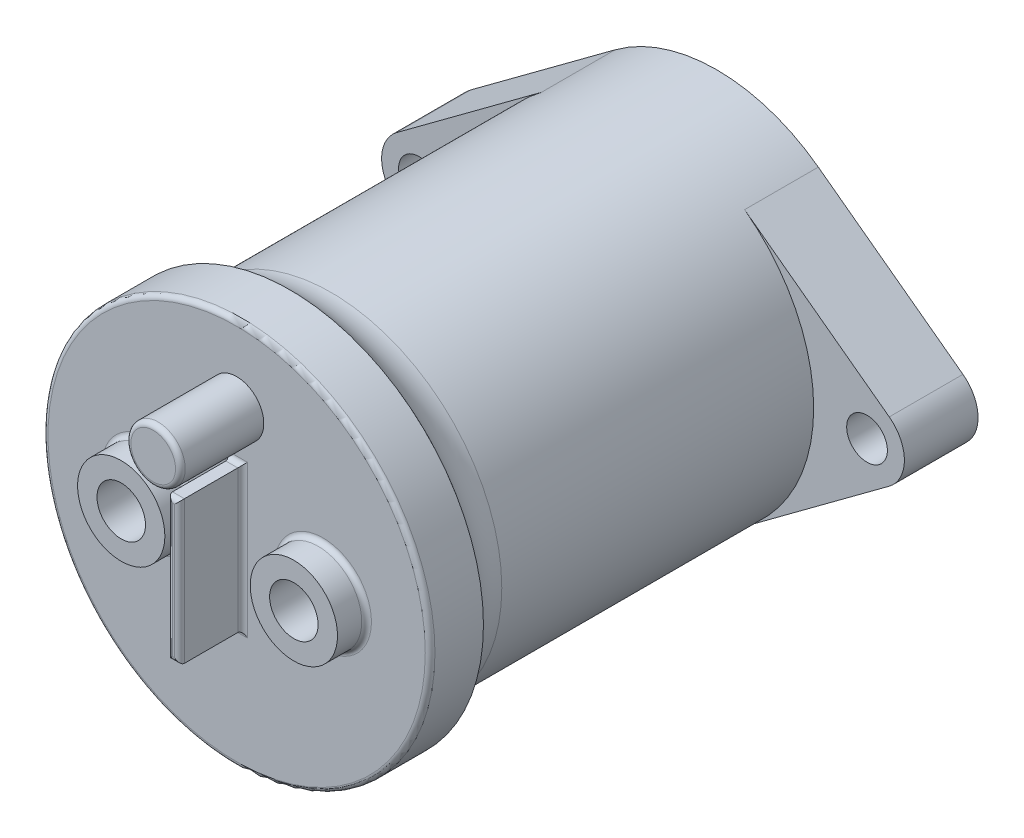
SolidWorks part; units mm, degrees
material "Custom Plastic"
ref_plane "X-Y Datum" through (0, 0, 0) normal (0, 0, 1) x (1, 0, 0)
ref_plane "X-Z Datum" through (0, 0, 0) normal (0, 1, 0) x (1, 0, 0)
ref_plane "Y-Z Datum" through (0, 0, 0) normal (1, 0, 0) x (0, 0, -1)
sketch "Sketch2" plane through (0, 0, 0) normal (0, 0, 1) x (1, 0, 0)
  circle A0 centre (0, 0) radius 17.6
  dimension "D1" = 35.2
extrude "Boss-Extrude1" add sketch "Sketch2" along normal blind 52.5
sketch "Sketch3" plane through (0, 0, 0) normal (0, 0, 1) x (1, 0, 0)
  line L0 (-23.1, 0) -> (23.1, 0) construction
  line L1 (-26.95, 0) -> (26.95, 0) construction
  line L2 (-25.3917, 3.0937) -> (-10.4762, 14.1425)
  line L3 (-25.3917, -3.0937) -> (-10.4762, -14.1425)
  line L4 (0, 28.5555) -> (0, -28.5555) construction
  line L5 (25.3917, -3.0937) -> (10.4762, -14.1425)
  line L6 (25.3917, 3.0937) -> (10.4762, 14.1425)
  circle A0 centre (23.1, 0) radius 2.1
  circle A1 centre (-23.1, 0) radius 2.1
  circle A2 centre (23.1, 0) radius 3.85
  circle A3 centre (-23.1, 0) radius 3.85
  circle A6 centre (0, 0) radius 17.6 construction
  circle A8 centre (0, 0) radius 17.6
  circle A9 centre (0, 0) radius 17.6
  point P4 (0, 0)
  point P10 (0, 0)
  point P23 (0, 0)
  dimension "D2" = 4.2
  dimension "D1" = 46.2
  dimension "D3" = 53.9
  dimension "D4" = 0
extrude "Boss-Extrude2" add sketch "Sketch3" along normal blind 7.6 contours A9 A2 L6 | A9 L5 A2 | A9 A2 A0 | A9 A3 A1 | A9 A3 L3 | A9 L2 A3 region at (-18.5342, 0, 0) region at (-21.417, 3.3412, 0) region at (18.5342, 0, 0) region at (26.4412, 1.683, 0)
sketch "Sketch4" plane through (0, 0, 52.5) normal (0, 0, 1) x (1, 0, 0)
  line L0 (-8.9, 0) -> (8.9, 0) construction
  line L1 (-0.615, 7.35) -> (0.615, 7.35)
  line L2 (-0.615, 7.35) -> (-0.615, -7.35)
  line L3 (-0.615, -7.35) -> (0.615, -7.35)
  line L4 (0.615, 7.35) -> (0.615, -7.35)
  line L5 (-0.615, 7.35) -> (0.615, -7.35) construction
  line L6 (-0.615, -7.35) -> (0.615, 7.35) construction
  circle A0 centre (-8.9, 0) radius 2.5
  circle A1 centre (8.9, 0) radius 2.5
  circle A2 centre (-8.9, 0) radius 4.5
  circle A3 centre (8.9, 0) radius 4.5
  point P0 (0, 0)
  point P11 (0, 0)
  dimension "D4" = 5
  dimension "D5" = 9
  dimension "D1" = 1.23
  dimension "D2" = 14.7
  dimension "D3" = 17.8
extrude "Boss-Extrude3" add sketch "Sketch4" along normal blind 3.5 contours L2 L1 L4 L3
sketch "Sketch5" plane through (0, 0, 52.5) normal (0, 0, 1) x (1, 0, 0)
  line L4 (0.615, 7.35) -> (-0.615, 7.35)
  line L5 (0.615, -7.35) -> (0.615, 7.35)
  line L6 (-0.615, -7.35) -> (0.615, -7.35)
  line L7 (-0.615, 7.35) -> (-0.615, -7.35)
  line L8 (0.615, 7.35) -> (-0.615, 7.35)
  line L9 (0.615, -7.35) -> (0.615, 7.35)
  line L10 (-0.615, -7.35) -> (0.615, -7.35)
  line L11 (-0.615, 7.35) -> (-0.615, -7.35)
  circle A1 centre (8.9, 0) radius 4.5
  circle A2 centre (8.9, 0) radius 4.5
  circle A3 centre (-8.9, 0) radius 4.5
  circle A4 centre (-8.9, 0) radius 4.5
  circle A5 centre (8.9, 0) radius 2.5
  circle A6 centre (8.9, 0) radius 2.5
  circle A7 centre (-8.9, 0) radius 2.5
  circle A8 centre (-8.9, 0) radius 2.5
  circle M22 centre (0, 0) radius 17.6
  line M23 (0.615, 7.35) -> (0.615, -7.35)
  line M24 (0.615, -7.35) -> (-0.615, -7.35)
  line M25 (-0.615, -7.35) -> (-0.615, 7.35)
  line M26 (-0.615, 7.35) -> (0.615, 7.35)
  dimension "D1" = 0
  dimension "D2" = 0
  dimension "D3" = 0
  dimension "D4" = 0
  dimension "D5" = 0
extrude "Cut-Extrude1" cut sketch "Sketch5" against normal blind 3 contours A4 A2 M22 M26 M23 M24 M25 | A8 | A6 region at (8.9, 0, 52.5) region at (-8.9, 0, 52.5) region at (-17.1022, 0, 52.5)
sketch "Sketch7" plane through (0, 0, 49.5) normal (0, 0, 1) x (1, 0, 0)
  circle A0 centre (0, 0) radius 19.95
  dimension "D1" = 39.9
extrude "Boss-Extrude5" add sketch "Sketch7" against normal blind 5.5
fillet "Fillet3" radius 5 1 edges at (17.6, 0, 44)
fillet "Fillet4" radius 0.5 11 edges at (-0.615, 0, 56) (0, 7.35, 56) (0.615, 0, 56) (0, -7.35, 56) (19.95, 0, 49.5) (-0.615, 0, 49.5) (0, -7.35, 49.5) (0.615, 0, 49.5) (0, 7.35, 49.5) (13.4, 0, 49.5) (-4.4, 0, 49.5)
sketch "Sketch8" plane through (0, 0, 52.5) normal (0, 0, 1) x (1, 0, 0)
  circle A0 centre (-8.9, 0) radius 2.5 construction
  circle A1 centre (8.9, 0) radius 2.5
  circle A2 centre (8.9, 0) radius 2.5
  circle A3 centre (-8.9, 0) radius 2.5
  dimension "D1" = 0
extrude "Cut-Extrude2" cut sketch "Sketch8" against normal blind 7
ref_plane "Plane1" through (0, 0, 0) normal (0.8035, 0.5952, 0) x (0, 0, 1)
sketch "Sketch10" plane through (0, 0, 49.5) normal (0, 0, 1) x (1, 0, 0)
  line L0 (0, 0) -> (0, 12.15) construction
  line L1 (0.615, 7.35) -> (-0.615, 7.35) construction
  circle A0 centre (0, 12.15) radius 2.8
  point P2 (0, 9.35)
  dimension "D1" = 5.6
  dimension "D2" = 2
extrude "Boss-Extrude6" add sketch "Sketch10" along normal blind 8.6
fillet "Fillet5" radius 0.5 1 edges at (2.8, 12.15, 58.1)
